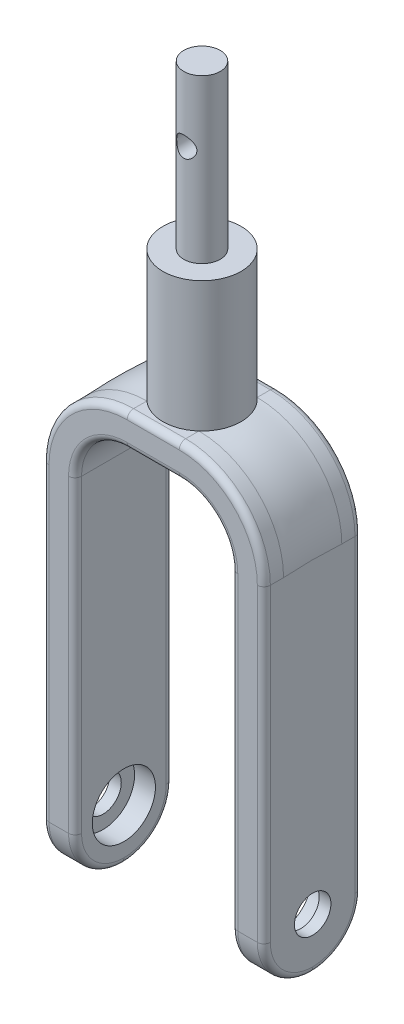
SolidWorks part; units mm, degrees
ref_plane "前视基准面" through (0, 0, 0) normal (0, 0, 1) x (1, 0, 0)
ref_plane "上视基准面" through (0, 0, 0) normal (0, 1, 0) x (1, 0, 0)
ref_plane "右视基准面" through (0, 0, 0) normal (1, 0, 0) x (0, 0, -1)
sketch "草图1" plane through (0, 0, 0) normal (0, 1, 0) x (1, 0, 0)
  line L1 (17, 7.5) -> (-17, 7.5)
  line L2 (17, 7.5) -> (17, -7.5)
  line L3 (17, -7.5) -> (-17, -7.5)
  line L4 (-17, 7.5) -> (-17, -7.5)
  line L5 (17, 7.5) -> (-17, -7.5) construction
  line L6 (17, -7.5) -> (-17, 7.5) construction
  point P0 (0, 0)
extrude "凸台-拉伸1" add sketch "草图1" against normal blind 68
sketch "草图2" plane through (0, 0, 0) normal (0, 1, 0) x (1, 0, 0)
  circle A0 centre (0, 0) radius 6
extrude "凸台-拉伸2" add sketch "草图2" along normal blind 20
sketch "草图7" plane through (0, 20, 0) normal (0, 1, 0) x (1, 0, 0)
  circle A0 centre (0, 0) radius 2.8
extrude "凸台-拉伸3" add sketch "草图7" along normal blind 25
sketch "草图8" plane through (0, 0, 0) normal (0, 0, 1) x (1, 0, 0)
  line L0 (0, 20) -> (0, 35) construction
  line L1 (6, 20) -> (-6, 20) construction
  circle A1 centre (0, 35) radius 1.55
extrude "切除-拉伸5" cut sketch "草图8" against normal through all both and the other way through all
sketch "草图3" plane through (0, 0, 7.5) normal (0, 0, 1) x (1, 0, 0)
  line L0 (-17, -68) -> (17, -68) construction
  line L1 (-12, -68) -> (12, -68)
  line L2 (-12, -68) -> (-12, -5)
  line L3 (-12, -5) -> (12, -5)
  line L4 (12, -68) -> (12, -5)
  point P6 (0, 0)
  point P7 (0, 0)
  point P8 (0, 0)
extrude "切除-拉伸1" cut sketch "草图3" against normal through all
fillet "圆角1" radius 8 2 edges at (12, -5, 0) (-12, -5, 0)
fillet "圆角5" radius 13 2 edges at (17, 0, 0) (-17, 0, 0)
fillet "圆角3" radius 7.5 4 edges at (14.5, -68, -7.5) (14.5, -68, 7.5) (-14.5, -68, -7.5) (-14.5, -68, 7.5)
fillet "圆角2" radius 1 28 edges at (-17, -36.75, -7.5) (0, 0, -7.5) (17, -36.75, -7.5) (17, -36.75, 7.5) (0, 0, 7.5) (-17, -36.75, 7.5) (-9.6569, -7.3431, 7.5) (0, -5, 7.5) (9.6569, -7.3431, 7.5) (12, -36.75, 7.5) (12, -36.75, -7.5) (9.6569, -7.3431, -7.5) (0, -5, -7.5) (-9.6569, -7.3431, -7.5) (-12, -36.75, -7.5) (-12, -36.75, 7.5) (12, -65.8033, 5.3033) (12, -65.8033, -5.3033) (-12, -65.8033, -5.3033) (-12, -65.8033, 5.3033) (-17, -65.8033, 5.3033) (-17, -65.8033, -5.3033) (17, -65.8033, -5.3033) (17, -65.8033, 5.3033) (-13.1924, -3.8076, -7.5) (13.1924, -3.8076, -7.5) (13.1924, -3.8076, 7.5) (-13.1924, -3.8076, 7.5)
sketch "草图4" plane through (17, 0, 0) normal (1, 0, 0) x (0, 0, -1)
  circle A0 centre (0, -60) radius 2.8
extrude "切除-拉伸2" cut sketch "草图4" against normal through all
sketch "草图6" plane through (12, 0, 0) normal (1, 0, 0) x (0, 0, -1)
  circle A0 centre (0, -60) radius 4.85
extrude "切除-拉伸4" cut sketch "草图6" along normal blind 3.2
mirror "镜向1" about plane through (0, 0, 0) normal (1, 0, 0) of "切除-拉伸4"
